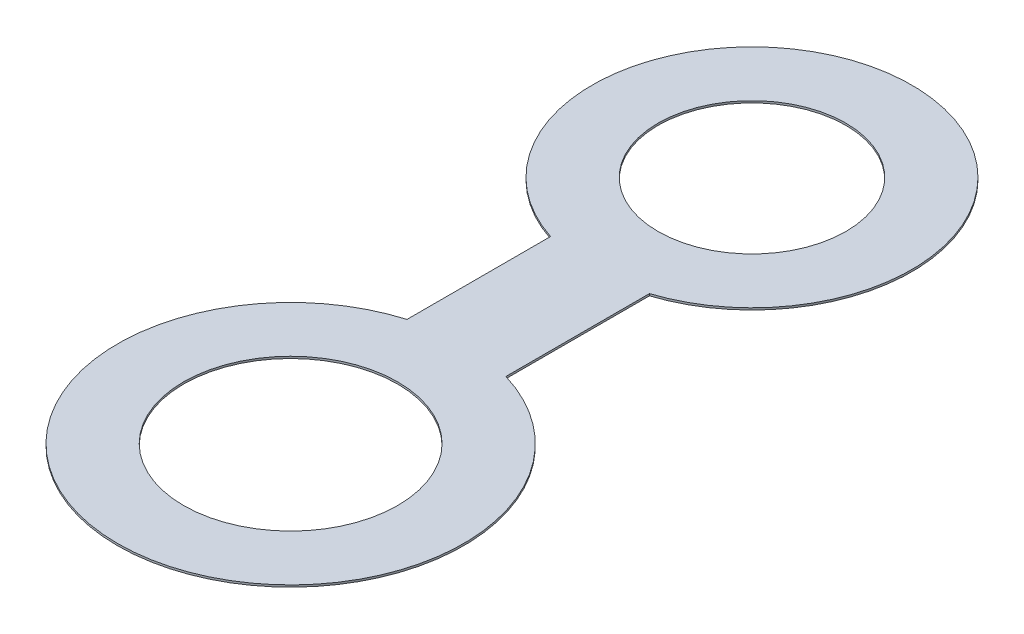
SolidWorks part; units mm, degrees
ref_plane "Front Plane" through (0, 0, 0) normal (0, 0, 1) x (1, 0, 0)
ref_plane "Top Plane" through (0, 0, 0) normal (0, 1, 0) x (1, 0, 0)
ref_plane "Right Plane" through (0, 0, 0) normal (1, 0, 0) x (0, 0, -1)
sketch "Sketch1" plane through (0, 0, 0) normal (0, 1, 0) x (1, 0, 0)
  line L1 (0, -75.7707) -> (0, 75.7707) construction
  line L2 (-7.5, 55.75) -> (7.5, 55.75)
  line L3 (-7.5, 55.75) -> (-7.5, 16.25)
  line L4 (-7.5, 16.25) -> (7.5, 16.25)
  line L5 (7.5, 55.75) -> (7.5, 16.25)
  line L6 (-7.5, 55.75) -> (7.5, 16.25) construction
  line L7 (-7.5, 16.25) -> (7.5, 55.75) construction
  circle A0 centre (0, 0) radius 16.25
  circle A1 centre (0, 70) radius 14.25
  circle A2 centre (0, 70) radius 24.25
  circle A3 centre (0, 0) radius 26.25
  point P11 (0, 55.75)
  point P15 (0, 36)
  dimension "D5" = 28.5
  dimension "D6" = 32.5
  dimension "D1" = 0
  dimension "D2" = 0
  dimension "D3" = 70
  dimension "D8" = 0
  dimension "D9" = 16.25
  dimension "D10" = 15
  dimension "D11" = 14.25
  dimension "D4" = 10
  dimension "D7" = 10
extrude "Boss-Extrude1" add sketch "Sketch1" along normal blind 0.3 contours L3 A3 L5 L4 A0 | L5 A3 L3 L4 | A3 L5 A2 L3 | L5 A2 L3 L2 A1 | L3 A2 L5 L2 | L5 L4 L3 L2 region at (-8.1775, 0, -51.3445) region at (0, 0, -50.9397) region at (0, 0, -36.0158) region at (0, 0, -21.0747) region at (-8.2348, 0, -20.7029)
equation "\"D11@Sketch1\"=\"D5@Sketch1\"/2"
equation "\"D9@Sketch1\"=\"D6@Sketch1\"/2"
